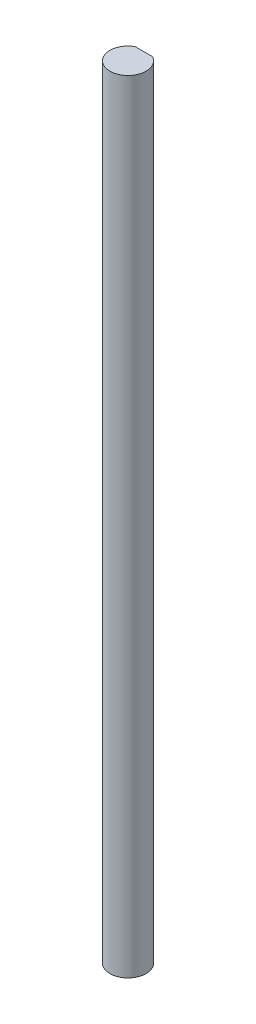
SolidWorks part; units mm, degrees
material "AISI 1045 Steel, cold drawn"
ref_plane "Front Plane" through (0, 0, 0) normal (0, 0, 1) x (1, 0, 0)
ref_plane "Top Plane" through (0, 0, 0) normal (0, 1, 0) x (1, 0, 0)
ref_plane "Right Plane" through (0, 0, 0) normal (1, 0, 0) x (0, 0, -1)
sketch "Sketch1" plane through (0, 0, 0) normal (0, 1, 0) x (1, 0, 0)
  line L0 (-1.9365, 3.5) -> (1.9365, 3.5)
  arc A0 (-1.9365, 3.5) -> (1.9365, 3.5) centre (0, 0) ccw
  dimension "D1" = 8
  dimension "D2" = 3.5
extrude "Boss-Extrude1" add sketch "Sketch1" along normal blind 173
